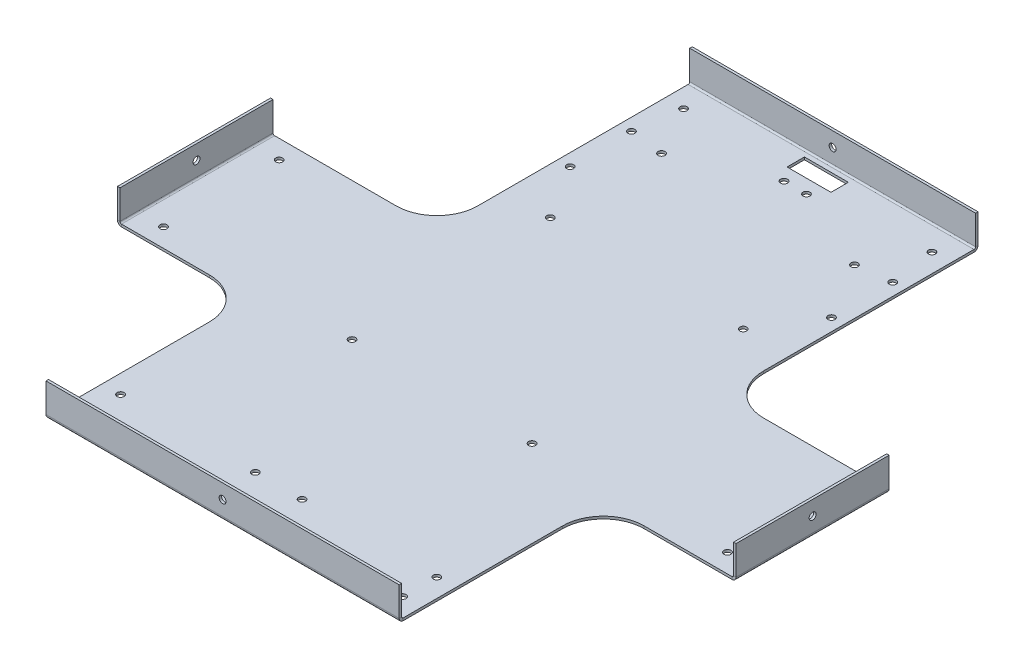
SolidWorks part; units mm, degrees
note: The reader was unsure of these and kept them because the rebuilt part matched: flange length of "Edge-Flange1", "Edge-Flange2", "Edge-Flange3".
material "Plain Carbon Steel"
ref_plane "Front Plane" through (0, 0, 0) normal (0, 0, 1) x (1, 0, 0)
ref_plane "Top Plane" through (0, 0, 0) normal (0, 1, 0) x (1, 0, 0)
ref_plane "Right Plane" through (0, 0, 0) normal (1, 0, 0) x (0, 0, -1)
sketch "Sketch1" plane through (0, 0, 0) normal (0, 1, 0) x (1, 0, 0)
  line L0 (86.5, 300) -> (86.5, 0) construction
  line L1 (0, 0) -> (173, 0)
  line L2 (0, 0) -> (0, 100)
  line L3 (16.5, 300) -> (156.5, 300)
  line L4 (173, 0) -> (173, 100)
  line L6 (0, 100) -> (-65, 100)
  line L7 (156.5, 175) -> (156.5, 300)
  line L8 (16.5, 175) -> (-65, 175)
  line L9 (-65, 100) -> (-65, 175)
  line L10 (16.5, 175) -> (16.5, 300)
  line L11 (156.5, 175) -> (238, 175)
  line L13 (173, 100) -> (238, 100)
  line L14 (238, 175) -> (238, 100)
  dimension "D1" = 300
  dimension "D2" = 173
  dimension "D3" = 100
  dimension "D4" = 65
  dimension "D5" = 125
  dimension "D6" = 100
  dimension "D7" = 125
  dimension "D8" = 65
  dimension "D9" = 140
base flange "Base-Flange1" sketch "Sketch1" thickness 1.21 reverse thickness direction no parameters "D1"=0.762
ref_plane "Mid Width Plane" through (86.5, 0, 0) normal (1, 0, 0) x (0, 0, -1)
hole_wizard "M3 Clearance Hole2" positions "Sketch29" profile "Sketch28" hole size "M3" standard "ANSI Metric"
sketch "Sketch29" plane through (0, -1.21, 0) normal (0, -1, 0) x (-1, 0, 0)
  point P0 (-9.052, 27.4796)
  point P3 (-75.052, 27.4796)
  point P6 (-42.4171, 107.4796)
sketch "Sketch28" plane through (9.052, -1.21, -27.4796) normal (1, 0, 0) x (0, 0, -1)
  line L0 (0, 0) -> (0, 2.2915)
  line L1 (0, 2.2915) -> (1.7, 1.27)
  line L2 (1.7, 1.27) -> (1.7, 0)
  line L5 (1.7, 0) -> (0, 0)
  line L10 (0, 2.2915) -> (-1.7, 1.27) construction
  line L11 (0, -6.35) -> (0, 107.95) construction
  dimension "Hole Dia." = 3.4
  dimension "Hole Depth" = 1.27
  dimension "Drill Angle" = 118
mirror "Mirror3" about plane through (86.5, 0, 0) normal (1, 0, 0) of "M3 Clearance Hole2"
fillet "Fillet1" radius 20 4 edges at (0, -0.605, -100) (173, -0.605, -100) (156.5, -0.605, -175) (16.5, -0.605, -175)
sketch "Sketch34" plane through (0, 0, 0) normal (0, 1, 0) x (1, 0, 0)
  line L0 (4.104, 114.5316) -> (80, 114.5316) construction
  line L1 (140.5, 119.5316) -> (32.5, 119.5316)
  line L2 (140.5, 119.5316) -> (140.5, 214.5316)
  line L3 (140.5, 214.5316) -> (32.5, 214.5316)
  line L4 (32.5, 119.5316) -> (32.5, 214.5316)
  line L5 (140.5, 119.5316) -> (32.5, 214.5316) construction
  line L6 (140.5, 214.5316) -> (32.5, 119.5316) construction
  line L9 (238, 100) -> (238, 175) construction
  point P0 (86.5, 167.0316)
  dimension "D1" = 95
  dimension "D2" = 108
  dimension "D3" = 52.5
  dimension "D4" = 151.5
sketch "Sketch35" plane through (0, 0, 0) normal (0, 1, 0) x (1, 0, 0)
  line L0 (140.5, 119.5316) -> (32.5, 119.5316) construction
  line L1 (147.5, 119.5316) -> (25.5, 119.5316)
  line L2 (147.5, 119.5316) -> (147.5, 132.5316)
  line L3 (147.5, 132.5316) -> (25.5, 132.5316)
  line L4 (25.5, 119.5316) -> (25.5, 132.5316)
  line L5 (147.5, 119.5316) -> (25.5, 132.5316) construction
  line L6 (147.5, 132.5316) -> (25.5, 119.5316) construction
  line L7 (32.5, 119.5316) -> (32.5, 214.5316) construction
  point P0 (86.5, 126.0316)
  dimension "D1" = 122
  dimension "D2" = 13
  dimension "D3" = 0
  dimension "D4" = 7
sketch "Sketch62" plane through (0, 0, 0) normal (0, 1, 0) x (1, 0, 0)
  line L0 (86.5, -55.3673) -> (86.5, 55.3673) construction
  line L1 (138.897, 204.6283) -> (38.2926, 204.6283)
  line L2 (138.897, 204.6283) -> (138.897, 264.6283)
  line L3 (138.897, 264.6283) -> (38.2926, 264.6283)
  line L4 (38.2926, 204.6283) -> (38.2926, 264.6283)
  line L5 (138.897, 204.6283) -> (38.2926, 264.6283) construction
  line L6 (138.897, 264.6283) -> (38.2926, 204.6283) construction
  line L7 (97.25, 295.738) -> (75.75, 295.738)
  line L8 (97.25, 295.738) -> (97.25, 287.238)
  line L9 (97.25, 287.238) -> (75.75, 287.238)
  line L10 (75.75, 295.738) -> (75.75, 287.238)
  line L11 (97.25, 295.738) -> (75.75, 287.238) construction
  line L12 (97.25, 287.238) -> (75.75, 295.738) construction
  line L14 (156.5, 300) -> (16.5, 300) construction
  point P0 (88.5948, 234.6283)
  point P5 (86.5, 291.488)
  dimension "D1" = 60
  dimension "D2" = 8.5
  dimension "D3" = 21.5
  dimension "D4" = 0
  dimension "D5" = 4.262
extrude "QRD Clearance" cut sketch "Sketch62" against normal blind 10 contours L10 L9 L8 L7 normal cut yes
sketch "Steering Box Allocation" plane through (0, 0, 0) normal (0, 1, 0) x (1, 0, 0)
  line L1 (161.5, 221.5316) -> (11.5, 221.5316)
  line L2 (161.5, 221.5316) -> (161.5, 291.5316)
  line L3 (161.5, 291.5316) -> (11.5, 291.5316)
  line L4 (11.5, 221.5316) -> (11.5, 291.5316)
  line L5 (161.5, 221.5316) -> (11.5, 291.5316) construction
  line L6 (161.5, 291.5316) -> (11.5, 221.5316) construction
  line L8 (140.5, 214.5316) -> (32.5, 214.5316) construction
  line L10 (86.5, -55.3673) -> (86.5, 55.3673) construction
  point P0 (86.5, 256.5316)
  dimension "D1" = 150
  dimension "D2" = 0
  dimension "D3" = 70
  dimension "D4" = 7
hole_wizard "QRD Holes" positions "Sketch75" profile "Sketch74" hole size "M3" standard "ANSI Metric"
sketch "Sketch75" plane through (0, 0, 0) normal (0, 1, 0) x (1, 0, 0)
  point P0 (92, 280.488)
  point P3 (81, 280.488)
sketch "Sketch74" plane through (92, 0, -280.488) normal (1, 0, 0) x (0, 0, 1)
  line L0 (0, 0) -> (0, 2.2915)
  line L1 (0, 2.2915) -> (1.7, 1.27)
  line L2 (1.7, 1.27) -> (1.7, 0)
  line L5 (1.7, 0) -> (0, 0)
  line L10 (0, 2.2915) -> (-1.7, 1.27) construction
  line L11 (0, -6.35) -> (0, 107.95) construction
  dimension "Hole Dia." = 3.4
  dimension "Hole Depth" = 1.27
  dimension "Drill Angle" = 118
sketch "Sketch73" plane through (0, 0, 0) normal (0, 1, 0) x (1, 0, 0)
  line L0 (16.5, 249.238) -> (200, 249.238)
  line L1 (16.5, 299.238) -> (16.5, 195) construction
  line L3 (16.5, 299.238) -> (156.5, 299.238) construction
  dimension "D1" = 50
hole_wizard "M3 (Steering Box)" positions "Sketch133" profile "Sketch132" hole size "M3" standard "ANSI Metric"
sketch "Sketch133" plane through (0, 0, 0) normal (0, 1, 0) x (1, 0, 0)
  point P0 (39.262, 262.238)
  point P3 (39.262, 207.762)
  point P6 (133.738, 207.762)
  point P9 (133.738, 262.238)
sketch "Sketch132" plane through (39.262, 0, -262.238) normal (1, 0, 0) x (0, 0, 1)
  line L0 (0, 0) -> (0, 4.0215)
  line L1 (0, 4.0215) -> (1.7, 3)
  line L2 (1.7, 3) -> (1.7, 0)
  line L5 (1.7, 0) -> (0, 0)
  line L10 (0, 4.0215) -> (-1.7, 3) construction
  line L11 (0, -6.35) -> (0, 107.95) construction
  dimension "Hole Dia." = 3.4
  dimension "Hole Depth" = 3
  dimension "Drill Angle" = 118
edge flange "Edge-Flange1" sketch "Sketch136" flange angle 90 flange length 15 flange position material inside bend radius 0.762 thickness 1.21 relief rectangular parameters "D6"=10
sketch "Sketch136" plane through (0, 0, 0) normal (0, 0, 1) x (1, 0, 0)
  line L2 (0, 0) -> (0, 15)
  line L3 (0, 15) -> (173, 15)
  line L4 (173, 15) -> (173, 0)
  line L5 (0, 0) -> (173, 0) construction
  line L6 (0, 0) -> (173, 0)
bend "EdgeBend1" bend radius 0.762 bend angle 90 parameters "D5"=1
edge flange "Edge-Flange2" sketch "Sketch139" flange angle 90 flange length 15 flange position material inside bend radius 0.762 thickness 1.21 relief rectangular parameters "D6"=10
sketch "Sketch139" plane through (0, 0, -300) normal (0, 0, -1) x (-1, 0, 0)
  line L0 (-156.5, 0) -> (-16.5, 0) construction
  line L1 (-156.5, 0) -> (-16.5, 0)
  line L2 (-156.5, 0) -> (-156.5, 15)
  line L3 (-156.5, 15) -> (-16.5, 15)
  line L4 (-16.5, 15) -> (-16.5, 0)
bend "EdgeBend2" bend radius 0.762 bend angle 90 parameters "D5"=2
edge flange "Edge-Flange3" sketch "Sketch142" flange angle 90 flange length 15 flange position material inside bend radius 0.762 thickness 1.21 relief rectangular parameters "D6"=10
sketch "Sketch142" plane through (238, 0, 0) normal (1, 0, 0) x (0, 0, -1)
  line L2 (100, 0) -> (100, 15)
  line L3 (100, 15) -> (175, 15)
  line L4 (175, 15) -> (175, 0)
  line L5 (100, 0) -> (175, 0) construction
  line L6 (100, 0) -> (175, 0)
bend "EdgeBend3" bend radius 0.762 bend angle 90 parameters "D5"=3
mirror "Mirror4" about plane through (86.5, 0, 0) normal (1, 0, 0) of "Edge-Flange3"
bend "MirrorBend1" bend radius 0.762 bend angle 90 parameters "D5"=4
hole_wizard "M3 Clearance Hole3" positions "Sketch143" profile "Sketch144" hole size "M3" standard "ANSI Metric" end condition through all
sketch "Sketch143" plane through (50.7661, 0, -139.8998) normal (0, 1, 0) x (1, 0, 0)
  point P0 (-28.2661, 124.3382)
  point P1 (-28.2661, 94.3382)
sketch "Sketch144" plane through (22.5, 0, -264.238) normal (1, 0, 0) x (0, 0, 1)
  line L0 (0, 0) -> (0, 1.21)
  line L1 (0, 1.21) -> (1.7, 1.21)
  line L2 (1.7, 1.21) -> (1.7, 0)
  line L3 (1.7, 0) -> (0, 0)
  line L4 (0, -6.35) -> (0, 107.95) construction
  dimension "Thru Hole Dia." = 3.4
  dimension "Thru Hole Depth" = 1.21
hole_wizard "M3 Clearance Hole4" positions "Sketch145" profile "Sketch146" hole size "M3" standard "ANSI Metric" end condition through all
sketch "Sketch145" plane through (50.7661, 0, -139.8998) normal (0, 1, 0) x (1, 0, 0)
  point P0 (99.7339, 124.3382)
  point P1 (99.7339, 94.3382)
sketch "Sketch146" plane through (150.5, 0, -264.238) normal (1, 0, 0) x (0, 0, 1)
  line L0 (0, 0) -> (0, 1.21)
  line L1 (0, 1.21) -> (1.7, 1.21)
  line L2 (1.7, 1.21) -> (1.7, 0)
  line L3 (1.7, 0) -> (0, 0)
  line L4 (0, -6.35) -> (0, 107.95) construction
  dimension "Thru Hole Dia." = 3.4
  dimension "Thru Hole Depth" = 1.21
hole_wizard "M3 Clearance Hole5" positions "Sketch148" profile "Sketch147" hole size "M3" standard "ANSI Metric" end condition up to next
sketch "Sketch148" plane through (0, 0, 0) normal (0, 0, 1) x (1, 0, 0)
  line L2 (86.5, 15) -> (86.5, 0.762) construction
  line L3 (173, 15) -> (0, 15) construction
  line L4 (173, 0.762) -> (0, 0.762) construction
  line L7 (173, 7.881) -> (0, 7.881) construction
  line L8 (173, 0.762) -> (173, 15) construction
  line L9 (0, 15) -> (0, 0.762) construction
  point P0 (86.5, 7.881)
sketch "Sketch147" plane through (86.5, 7.881, 0) normal (1, 0, 0) x (0, -1, 0)
  line L0 (0, 0) -> (0, 1.21)
  line L1 (0, 1.21) -> (1.7, 1.21)
  line L2 (1.7, 1.21) -> (1.7, 0)
  line L5 (1.7, 0) -> (0, 0)
  line L11 (0, -6.35) -> (0, 107.95) construction
  dimension "Thru Hole Dia." = 3.4
  dimension "Thru Hole Depth" = 1.21
hole_wizard "M3 Clearance Hole6" positions "Sketch150" profile "Sketch149" hole size "M3" standard "ANSI Metric" end condition through all
sketch "Sketch150" plane through (238, 0, 0) normal (1, 0, 0) x (0, 0, -1)
  line L0 (100, 7.881) -> (175, 7.881) construction
  line L1 (100, 15) -> (100, 0.762) construction
  line L2 (175, 0.762) -> (175, 15) construction
  line L4 (137.5, 15) -> (137.5, 0.762) construction
  line L5 (175, 15) -> (100, 15) construction
  line L6 (175, 0.762) -> (100, 0.762) construction
  point P0 (137.5, 7.881)
sketch "Sketch149" plane through (238, 7.881, -137.5) normal (0, 1, 0) x (0, 0, -1)
  line L0 (0, 0) -> (0, 303)
  line L1 (0, 303) -> (1.7, 303)
  line L2 (1.7, 303) -> (1.7, 0)
  line L5 (1.7, 0) -> (0, 0)
  line L11 (0, -6.35) -> (0, 107.95) construction
  dimension "Thru Hole Dia." = 3.4
  dimension "Thru Hole Depth" = 303
hole_wizard "M3 Clearance Hole7" positions "Sketch154" profile "Sketch153" hole size "M3" standard "ANSI Metric"
sketch "Sketch154" plane through (0, 0, -300) normal (0, 0, -1) x (-1, 0, 0)
  line L0 (-156.5, 7.881) -> (-16.5, 7.881) construction
  line L1 (-156.5, 15) -> (-156.5, 0.762) construction
  line L2 (-16.5, 0.762) -> (-16.5, 15) construction
  line L4 (-86.5, 15) -> (-86.5, 0.762) construction
  line L5 (-16.5, 15) -> (-156.5, 15) construction
  line L6 (-16.5, 0.762) -> (-156.5, 0.762) construction
  point P0 (-86.5, 7.881)
sketch "Sketch153" plane through (86.5, 7.881, -300) normal (1, 0, 0) x (0, 1, 0)
  line L0 (0, 0) -> (0, 2.2315)
  line L1 (0, 2.2315) -> (1.7, 1.21)
  line L2 (1.7, 1.21) -> (1.7, 0)
  line L5 (1.7, 0) -> (0, 0)
  line L10 (0, 2.2315) -> (-1.7, 1.21) construction
  line L11 (0, -6.35) -> (0, 107.95) construction
  dimension "Hole Dia." = 3.4
  dimension "Hole Depth" = 1.21
  dimension "Drill Angle" = 118
hole_wizard "M3 Clearance Hole8" positions "Sketch155" profile "Sketch156" hole size "M3" standard "ANSI Metric" end condition through all
sketch "Sketch155" plane through (50.7661, 0, -139.8998) normal (0, 1, 0) x (1, 0, 0)
  point P0 (-25.0951, 146.7192)
  point P1 (96.5629, 146.7192)
sketch "Sketch156" plane through (25.671, 0, -286.619) normal (1, 0, 0) x (0, 0, 1)
  line L0 (0, 0) -> (0, 1.21)
  line L1 (0, 1.21) -> (1.7, 1.21)
  line L2 (1.7, 1.21) -> (1.7, 0)
  line L3 (1.7, 0) -> (0, 0)
  line L4 (0, -6.35) -> (0, 107.95) construction
  dimension "Thru Hole Dia." = 3.4
  dimension "Thru Hole Depth" = 1.21
hole_wizard "M3 Clearance Hole9" positions "Sketch157" profile "Sketch158" hole size "M3" standard "ANSI Metric" end condition through all
sketch "Sketch157" plane through (50.7661, 0, -139.8998) normal (0, 1, 0) x (1, 0, 0)
  point P0 (-102.3851, -30.7288)
  point P1 (-102.3851, 25.9292)
sketch "Sketch158" plane through (-51.619, 0, -109.171) normal (1, 0, 0) x (0, 0, 1)
  line L0 (0, 0) -> (0, 1.21)
  line L1 (0, 1.21) -> (1.7, 1.21)
  line L2 (1.7, 1.21) -> (1.7, 0)
  line L3 (1.7, 0) -> (0, 0)
  line L4 (0, -6.35) -> (0, 107.95) construction
  dimension "Thru Hole Dia." = 3.4
  dimension "Thru Hole Depth" = 1.21
hole_wizard "M3 Clearance Hole10" positions "Sketch159" profile "Sketch160" hole size "M3" standard "ANSI Metric" end condition through all
sketch "Sketch159" plane through (50.7661, 0, -139.8998) normal (0, 1, 0) x (1, 0, 0)
  point P0 (173.8529, 25.9292)
  point P1 (173.8529, -30.7288)
sketch "Sketch160" plane through (224.619, 0, -165.829) normal (1, 0, 0) x (0, 0, 1)
  line L0 (0, 0) -> (0, 1.21)
  line L1 (0, 1.21) -> (1.7, 1.21)
  line L2 (1.7, 1.21) -> (1.7, 0)
  line L3 (1.7, 0) -> (0, 0)
  line L4 (0, -6.35) -> (0, 107.95) construction
  dimension "Thru Hole Dia." = 3.4
  dimension "Thru Hole Depth" = 1.21
hole_wizard "M3 Clearance Hole11" positions "Sketch161" profile "Sketch162" hole size "M3" standard "ANSI Metric" end condition through all
sketch "Sketch161" plane through (50.7661, 0, -139.8998) normal (0, 1, 0) x (1, 0, 0)
  point P0 (113.0629, -129.0188)
  point P1 (-41.5951, -129.0188)
sketch "Sketch162" plane through (163.829, 0, -10.881) normal (1, 0, 0) x (0, 0, 1)
  line L0 (0, 0) -> (0, 1.21)
  line L1 (0, 1.21) -> (1.7, 1.21)
  line L2 (1.7, 1.21) -> (1.7, 0)
  line L3 (1.7, 0) -> (0, 0)
  line L4 (0, -6.35) -> (0, 107.95) construction
  dimension "Thru Hole Dia." = 3.4
  dimension "Thru Hole Depth" = 1.21
sketch "Bend-Lines1" [suppressed] plane through (0, 0, 0) normal (0, 1, 0) x (1, 0, 0)
sketch "Bounding-Box1" [suppressed] plane through (0, 0, 0) normal (0, 1, 0) x (1, 0, 0)
sheet metal parameters "Sheet-Metal(1)" thickness 1.21 parameters "D1"=0.762
flat pattern "Flat-Pattern(1)" [suppressed]
sketch "Bend-Lines2" plane through (0, 0, 0) normal (0, 1, 0) x (1, 0, 0)
sketch "Bounding-Box2" [suppressed] plane through (0, 0, 0) normal (0, 1, 0) x (1, 0, 0)
sheet metal parameters "Sheet-Metal(23)" thickness 1.21 parameters "D1"=0.762
flat pattern "Flat-Pattern(1)"
sketch "Bend-Lines2" plane through (0, 0, 0) normal (0, 1, 0) x (1, 0, 0)
sketch "Bounding-Box2" [suppressed] plane through (0, 0, 0) normal (0, 1, 0) x (1, 0, 0)
sheet metal parameters "Sheet-Metal(24)" thickness 1.21 parameters "D1"=0.762
flat pattern "Flat-Pattern(1)"
sketch "Bend-Lines2" plane through (0, 0, 0) normal (0, 1, 0) x (1, 0, 0)
sketch "Bounding-Box2" [suppressed] plane through (0, 0, 0) normal (0, 1, 0) x (1, 0, 0)
sheet metal parameters "Sheet-Metal(36)" thickness 1.21 parameters "D1"=0.762
flat pattern "Flat-Pattern(1)"
sketch "Bend-Lines2" plane through (0, 0, 0) normal (0, 1, 0) x (1, 0, 0)
sketch "Bounding-Box2" [suppressed] plane through (0, 0, 0) normal (0, 1, 0) x (1, 0, 0)
sheet metal parameters "Sheet-Metal(39)" thickness 1.21 parameters "D1"=0.762
flat pattern "Flat-Pattern(1)"
sketch "Bend-Lines2" plane through (0, 0, 0) normal (0, 1, 0) x (1, 0, 0)
sketch "Bounding-Box2" [suppressed] plane through (0, 0, 0) normal (0, 1, 0) x (1, 0, 0)
sheet metal parameters "Sheet-Metal(71)" thickness 1.21 parameters "D1"=0.762
flat pattern "Flat-Pattern(1)"
sketch "Bend-Lines2" plane through (0, 0, 0) normal (0, 1, 0) x (1, 0, 0)
  line L0 (0, -74.1425) -> (173, -74.1425) construction
  line L1 (372.6314, 94.104) -> (372.6314, 200) construction
  line L2 (352.7291, 94.104) -> (352.7291, 200) construction
  line L3 (331.5548, 94.104) -> (331.5548, 200) construction
  line L4 (-199.6314, 200) -> (-199.6314, 94.104) construction
  line L5 (-179.7291, 200) -> (-179.7291, 94.104) construction
  line L6 (-158.5548, 200) -> (-158.5548, 94.104) construction
  line L7 (173, 372.3805) -> (0, 372.3805) construction
  line L8 (310.3805, 94.104) -> (310.3805, 200) construction
  line L9 (-137.3805, 200) -> (-137.3805, 94.104) construction
  line L10 (147.5, 100.0722) -> (25.5, 100.0722) construction
  line L11 (0, -1.9682) -> (173, -1.9682) construction
  line L12 (-65.2062, 200) -> (-65.2062, 94.104) construction
  line L13 (173, 300.2062) -> (0, 300.2062) construction
  line L14 (238.2062, 94.104) -> (238.2062, 200) construction
  line L15 (0, -74.1425) -> (173, -74.1425) construction
  line L16 (372.6314, 94.104) -> (372.6314, 200) construction
  line L17 (352.7291, 94.104) -> (352.7291, 200) construction
  line L18 (331.5548, 94.104) -> (331.5548, 200) construction
  line L19 (-199.6314, 200) -> (-199.6314, 94.104) construction
  line L20 (-179.7291, 200) -> (-179.7291, 94.104) construction
  line L21 (-158.5548, 200) -> (-158.5548, 94.104) construction
  line L22 (173, 372.3805) -> (0, 372.3805) construction
  line L23 (310.3805, 94.104) -> (310.3805, 200) construction
  line L24 (-137.3805, 200) -> (-137.3805, 94.104) construction
  line L25 (147.5, 100.0722) -> (25.5, 100.0722) construction
  line L26 (0, -1.9682) -> (173, -1.9682) construction
  line L27 (-65.2062, 200) -> (-65.2062, 94.104) construction
  line L28 (173, 300.2062) -> (0, 300.2062) construction
  line L29 (238.2062, 94.104) -> (238.2062, 200) construction
sketch3d "Bounding-Box2" [suppressed]
  line L0 (-268.2639, 140.3537, 0) -> (126.5382, -205.5089, 0) construction
  line L1 (46.4618, 499.6129, 0) -> (441.2639, 153.7503, 0) construction
  line L2 (-268.2639, 140.3537, 0) -> (46.4618, 499.6129, 0) construction
  line L3 (126.5382, -205.5089, 0) -> (441.2639, 153.7503, 0) construction
sheet metal parameters "Sheet-Metal(103)" thickness 1.21 parameters "D1"=0.762
flat pattern "Flat-Pattern(1)" [suppressed]
sketch "Bend-Lines2" plane through (0, 0, 0) normal (0, 1, 0) x (1, 0, 0)
  line L0 (0, -74.1425) -> (173, -74.1425) construction
  line L1 (372.6314, 94.104) -> (372.6314, 200) construction
  line L2 (352.7291, 94.104) -> (352.7291, 200) construction
  line L3 (331.5548, 94.104) -> (331.5548, 200) construction
  line L4 (-199.6314, 200) -> (-199.6314, 94.104) construction
  line L5 (-179.7291, 200) -> (-179.7291, 94.104) construction
  line L6 (-158.5548, 200) -> (-158.5548, 94.104) construction
  line L7 (173, 372.3805) -> (0, 372.3805) construction
  line L8 (310.3805, 94.104) -> (310.3805, 200) construction
  line L9 (-137.3805, 200) -> (-137.3805, 94.104) construction
  line L10 (147.5, 100.0722) -> (25.5, 100.0722) construction
  line L11 (0, -1.9682) -> (173, -1.9682) construction
  line L12 (-65.2062, 200) -> (-65.2062, 94.104) construction
  line L13 (173, 300.2062) -> (0, 300.2062) construction
  line L14 (238.2062, 94.104) -> (238.2062, 200) construction
  line L15 (0, -74.1425) -> (173, -74.1425) construction
  line L16 (372.6314, 94.104) -> (372.6314, 200) construction
  line L17 (352.7291, 94.104) -> (352.7291, 200) construction
  line L18 (331.5548, 94.104) -> (331.5548, 200) construction
  line L19 (-199.6314, 200) -> (-199.6314, 94.104) construction
  line L20 (-179.7291, 200) -> (-179.7291, 94.104) construction
  line L21 (-158.5548, 200) -> (-158.5548, 94.104) construction
  line L22 (173, 372.3805) -> (0, 372.3805) construction
  line L23 (310.3805, 94.104) -> (310.3805, 200) construction
  line L24 (-137.3805, 200) -> (-137.3805, 94.104) construction
  line L25 (147.5, 100.0722) -> (25.5, 100.0722) construction
  line L26 (0, -1.9682) -> (173, -1.9682) construction
  line L27 (-65.2062, 200) -> (-65.2062, 94.104) construction
  line L28 (173, 300.2062) -> (0, 300.2062) construction
  line L29 (238.2062, 94.104) -> (238.2062, 200) construction
sketch3d "Bounding-Box2" [suppressed]
  line L0 (-268.2639, 140.3537, 0) -> (126.5382, -205.5089, 0) construction
  line L1 (46.4618, 499.6129, 0) -> (441.2639, 153.7503, 0) construction
  line L2 (-268.2639, 140.3537, 0) -> (46.4618, 499.6129, 0) construction
  line L3 (126.5382, -205.5089, 0) -> (441.2639, 153.7503, 0) construction
bend of the flat pattern "Flatten-<EdgeBend1>1"
sheet metal parameters "Sheet-Metal(104)" thickness 1.21 parameters "D1"=0.762
flat pattern "Flat-Pattern(1)"
sketch "Bend-Lines2" plane through (0, 0, 0) normal (0, 1, 0) x (1, 0, 0)
  line L30 (18.5, 298.9962) -> (154.5, 298.9962) construction
  line L31 (171, 1.0038) -> (2, 1.0038) construction
  line L32 (18.5, 298.9962) -> (154.5, 298.9962) construction
  line L33 (171, 1.0038) -> (2, 1.0038) construction
sketch3d "Bounding-Box2" [suppressed]
  line L0 (238.0001, 314.2023, 0) -> (237.9999, -14.2023, 0) construction
  line L1 (-64.9999, 314.2024, 0) -> (-65.0001, -14.2022, 0) construction
  line L2 (238.0001, 314.2023, 0) -> (-64.9999, 314.2024, 0) construction
  line L3 (237.9999, -14.2023, 0) -> (-65.0001, -14.2022, 0) construction
bend of the flat pattern "Flatten-<EdgeBend1>1"
bend of the flat pattern "Flatten-<EdgeBend2>1"
sheet metal parameters "Sheet-Metal(105)" thickness 1.21 parameters "D1"=0.762
flat pattern "Flat-Pattern(1)" [suppressed]
sketch "Bend-Lines2" plane through (0, 0, 0) normal (0, 1, 0) x (1, 0, 0)
  line L30 (18.5, 298.9962) -> (154.5, 298.9962) construction
  line L31 (171, 1.0038) -> (2, 1.0038) construction
  line L32 (18.5, 298.9962) -> (154.5, 298.9962) construction
  line L33 (171, 1.0038) -> (2, 1.0038) construction
sketch3d "Bounding-Box2" [suppressed]
  line L0 (238.0001, 314.2023, 0) -> (237.9999, -14.2023, 0) construction
  line L1 (-64.9999, 314.2024, 0) -> (-65.0001, -14.2022, 0) construction
  line L2 (238.0001, 314.2023, 0) -> (-64.9999, 314.2024, 0) construction
  line L3 (237.9999, -14.2023, 0) -> (-65.0001, -14.2022, 0) construction
bend of the flat pattern "Flatten-<EdgeBend1>1"
bend of the flat pattern "Flatten-<EdgeBend3>1"
bend of the flat pattern "Flatten-<EdgeBend2>1"
sheet metal parameters "Sheet-Metal(106)" thickness 1.21 parameters "D1"=0.762
flat pattern "Flat-Pattern(1)" [suppressed]
sketch "Bend-Lines2" plane through (0, 0, 0) normal (0, 1, 0) x (1, 0, 0)
  line L30 (18.5, 298.9962) -> (154.5, 298.9962) construction
  line L31 (171, 1.0038) -> (2, 1.0038) construction
  line L32 (18.5, 298.9962) -> (154.5, 298.9962) construction
  line L33 (171, 1.0038) -> (2, 1.0038) construction
sketch3d "Bounding-Box2" [suppressed]
  line L0 (238.0001, 314.2023, 0) -> (237.9999, -14.2023, 0) construction
  line L1 (-64.9999, 314.2024, 0) -> (-65.0001, -14.2022, 0) construction
  line L2 (238.0001, 314.2023, 0) -> (-64.9999, 314.2024, 0) construction
  line L3 (237.9999, -14.2023, 0) -> (-65.0001, -14.2022, 0) construction
bend of the flat pattern "Flatten-<EdgeBend1>1"
bend of the flat pattern "Flatten-<EdgeBend3>1"
bend of the flat pattern "Flatten-<MirrorBend1>1"
bend of the flat pattern "Flatten-<EdgeBend2>1"
sheet metal parameters "Sheet-Metal(107)" thickness 1.21 parameters "D1"=0.762
flat pattern "Flat-Pattern(1)" [suppressed]
sketch "Bend-Lines2" plane through (0, 0, 0) normal (0, 1, 0) x (1, 0, 0)
  line L30 (18.5, 298.9962) -> (154.5, 298.9962) construction
  line L31 (171, 1.0038) -> (2, 1.0038) construction
  line L32 (18.5, 298.9962) -> (154.5, 298.9962) construction
  line L33 (171, 1.0038) -> (2, 1.0038) construction
sketch3d "Bounding-Box2" [suppressed]
  line L0 (238.0001, 314.2023, 0) -> (237.9999, -14.2023, 0) construction
  line L1 (-64.9999, 314.2024, 0) -> (-65.0001, -14.2022, 0) construction
  line L2 (238.0001, 314.2023, 0) -> (-64.9999, 314.2024, 0) construction
  line L3 (237.9999, -14.2023, 0) -> (-65.0001, -14.2022, 0) construction
bend of the flat pattern "Flatten-<EdgeBend1>1"
bend of the flat pattern "Flatten-<EdgeBend3>1"
bend of the flat pattern "Flatten-<MirrorBend1>1"
bend of the flat pattern "Flatten-<EdgeBend2>1"
sheet metal parameters "Sheet-Metal(108)" thickness 1.21 parameters "D1"=0.762
flat pattern "Flat-Pattern(1)" [suppressed]
sketch "Bend-Lines2" plane through (0, 0, 0) normal (0, 1, 0) x (1, 0, 0)
  line L30 (18.5, 298.9962) -> (154.5, 298.9962) construction
  line L31 (171, 1.0038) -> (2, 1.0038) construction
  line L32 (18.5, 298.9962) -> (154.5, 298.9962) construction
  line L33 (171, 1.0038) -> (2, 1.0038) construction
sketch3d "Bounding-Box2" [suppressed]
  line L0 (238.0001, 314.2023, 0) -> (237.9999, -14.2023, 0) construction
  line L1 (-64.9999, 314.2024, 0) -> (-65.0001, -14.2022, 0) construction
  line L2 (238.0001, 314.2023, 0) -> (-64.9999, 314.2024, 0) construction
  line L3 (237.9999, -14.2023, 0) -> (-65.0001, -14.2022, 0) construction
bend of the flat pattern "Flatten-<EdgeBend1>1"
bend of the flat pattern "Flatten-<EdgeBend3>1"
bend of the flat pattern "Flatten-<MirrorBend1>1"
bend of the flat pattern "Flatten-<EdgeBend2>1"
sheet metal parameters "Sheet-Metal(109)" thickness 1.21 parameters "D1"=0.762
flat pattern "Flat-Pattern(1)" [suppressed]
sketch "Bend-Lines2" plane through (0, 0, 0) normal (0, 1, 0) x (1, 0, 0)
  line L30 (18.5, 298.9962) -> (154.5, 298.9962) construction
  line L31 (171, 1.0038) -> (2, 1.0038) construction
  line L32 (18.5, 298.9962) -> (154.5, 298.9962) construction
  line L33 (171, 1.0038) -> (2, 1.0038) construction
sketch3d "Bounding-Box2" [suppressed]
  line L0 (238.0001, 314.2023, 0) -> (237.9999, -14.2023, 0) construction
  line L1 (-64.9999, 314.2024, 0) -> (-65.0001, -14.2022, 0) construction
  line L2 (238.0001, 314.2023, 0) -> (-64.9999, 314.2024, 0) construction
  line L3 (237.9999, -14.2023, 0) -> (-65.0001, -14.2022, 0) construction
bend of the flat pattern "Flatten-<EdgeBend1>1"
bend of the flat pattern "Flatten-<EdgeBend3>1"
bend of the flat pattern "Flatten-<MirrorBend1>1"
bend of the flat pattern "Flatten-<EdgeBend2>1"
sheet metal parameters "Sheet-Metal(110)" thickness 1.21 parameters "D1"=0.762
flat pattern "Flat-Pattern(1)" [suppressed]
sketch "Bend-Lines2" plane through (0, 0, 0) normal (0, 1, 0) x (1, 0, 0)
  line L30 (18.5, 298.9962) -> (154.5, 298.9962) construction
  line L31 (171, 1.0038) -> (2, 1.0038) construction
  line L32 (18.5, 298.9962) -> (154.5, 298.9962) construction
  line L33 (171, 1.0038) -> (2, 1.0038) construction
sketch3d "Bounding-Box2" [suppressed]
  line L0 (238.0001, 314.2023, 0) -> (237.9999, -14.2023, 0) construction
  line L1 (-64.9999, 314.2024, 0) -> (-65.0001, -14.2022, 0) construction
  line L2 (238.0001, 314.2023, 0) -> (-64.9999, 314.2024, 0) construction
  line L3 (237.9999, -14.2023, 0) -> (-65.0001, -14.2022, 0) construction
bend of the flat pattern "Flatten-<EdgeBend1>1"
bend of the flat pattern "Flatten-<EdgeBend3>1"
bend of the flat pattern "Flatten-<MirrorBend1>1"
bend of the flat pattern "Flatten-<EdgeBend2>1"
sheet metal parameters "Sheet-Metal(111)" thickness 1.21 parameters "D1"=0.762
flat pattern "Flat-Pattern(1)" [suppressed]
sketch "Bend-Lines2" plane through (0, 0, 0) normal (0, 1, 0) x (1, 0, 0)
  line L30 (18.5, 298.9962) -> (154.5, 298.9962) construction
  line L31 (171, 1.0038) -> (2, 1.0038) construction
  line L32 (18.5, 298.9962) -> (154.5, 298.9962) construction
  line L33 (171, 1.0038) -> (2, 1.0038) construction
sketch3d "Bounding-Box2" [suppressed]
  line L0 (238.0001, 314.2023, 0) -> (237.9999, -14.2023, 0) construction
  line L1 (-64.9999, 314.2024, 0) -> (-65.0001, -14.2022, 0) construction
  line L2 (238.0001, 314.2023, 0) -> (-64.9999, 314.2024, 0) construction
  line L3 (237.9999, -14.2023, 0) -> (-65.0001, -14.2022, 0) construction
bend of the flat pattern "Flatten-<EdgeBend1>1"
bend of the flat pattern "Flatten-<EdgeBend3>1"
bend of the flat pattern "Flatten-<MirrorBend1>1"
bend of the flat pattern "Flatten-<EdgeBend2>1"
sheet metal parameters "Sheet-Metal(112)" thickness 1.21 parameters "D1"=0.762
flat pattern "Flat-Pattern(1)" [suppressed]
sketch "Bend-Lines2" plane through (0, 0, 0) normal (0, 1, 0) x (1, 0, 0)
  line L30 (18.5, 298.9962) -> (154.5, 298.9962) construction
  line L31 (171, 1.0038) -> (2, 1.0038) construction
  line L32 (18.5, 298.9962) -> (154.5, 298.9962) construction
  line L33 (171, 1.0038) -> (2, 1.0038) construction
sketch3d "Bounding-Box2" [suppressed]
  line L0 (238.0001, 314.2023, 0) -> (237.9999, -14.2023, 0) construction
  line L1 (-64.9999, 314.2024, 0) -> (-65.0001, -14.2022, 0) construction
  line L2 (238.0001, 314.2023, 0) -> (-64.9999, 314.2024, 0) construction
  line L3 (237.9999, -14.2023, 0) -> (-65.0001, -14.2022, 0) construction
bend of the flat pattern "Flatten-<EdgeBend1>1"
bend of the flat pattern "Flatten-<EdgeBend3>1"
bend of the flat pattern "Flatten-<MirrorBend1>1"
bend of the flat pattern "Flatten-<EdgeBend2>1"
sheet metal parameters "Sheet-Metal(113)" thickness 1.21 parameters "D1"=0.762
flat pattern "Flat-Pattern(1)" [suppressed]
sketch "Bend-Lines2" plane through (0, 0, 0) normal (0, 1, 0) x (1, 0, 0)
  line L30 (18.5, 298.9962) -> (154.5, 298.9962) construction
  line L31 (171, 1.0038) -> (2, 1.0038) construction
  line L32 (18.5, 298.9962) -> (154.5, 298.9962) construction
  line L33 (171, 1.0038) -> (2, 1.0038) construction
sketch3d "Bounding-Box2" [suppressed]
  line L0 (238.0001, 314.2023, 0) -> (237.9999, -14.2023, 0) construction
  line L1 (-64.9999, 314.2024, 0) -> (-65.0001, -14.2022, 0) construction
  line L2 (238.0001, 314.2023, 0) -> (-64.9999, 314.2024, 0) construction
  line L3 (237.9999, -14.2023, 0) -> (-65.0001, -14.2022, 0) construction
bend of the flat pattern "Flatten-<EdgeBend1>1"
bend of the flat pattern "Flatten-<EdgeBend3>1"
bend of the flat pattern "Flatten-<MirrorBend1>1"
bend of the flat pattern "Flatten-<EdgeBend2>1"
sheet metal parameters "Sheet-Metal(114)" thickness 1.21 parameters "D1"=0.762
flat pattern "Flat-Pattern(1)" [suppressed]
sketch "Bend-Lines2" plane through (0, 0, 0) normal (0, 1, 0) x (1, 0, 0)
  line L30 (18.5, 298.9962) -> (154.5, 298.9962) construction
  line L31 (171, 1.0038) -> (2, 1.0038) construction
  line L32 (18.5, 298.9962) -> (154.5, 298.9962) construction
  line L33 (171, 1.0038) -> (2, 1.0038) construction
sketch3d "Bounding-Box2" [suppressed]
  line L0 (238.0001, 314.2023, 0) -> (237.9999, -14.2023, 0) construction
  line L1 (-64.9999, 314.2024, 0) -> (-65.0001, -14.2022, 0) construction
  line L2 (238.0001, 314.2023, 0) -> (-64.9999, 314.2024, 0) construction
  line L3 (237.9999, -14.2023, 0) -> (-65.0001, -14.2022, 0) construction
bend of the flat pattern "Flatten-<EdgeBend1>1"
bend of the flat pattern "Flatten-<EdgeBend3>1"
bend of the flat pattern "Flatten-<MirrorBend1>1"
bend of the flat pattern "Flatten-<EdgeBend2>1"
sheet metal parameters "Sheet-Metal(115)" thickness 1.21 parameters "D1"=0.762
flat pattern "Flat-Pattern(1)"
sketch "Bend-Lines2" plane through (0, 0, 0) normal (0, 1, 0) x (1, 0, 0)
  line L0 (-63.9962, 175) -> (-63.9962, 100) construction
  line L1 (236.9962, 100) -> (236.9962, 175) construction
  line L2 (-63.9962, 175) -> (-63.9962, 100) construction
  line L3 (236.9962, 100) -> (236.9962, 175) construction
  line L30 (156.5, 298.9962) -> (16.5, 298.9962) construction
  line L31 (0, 1.0038) -> (173, 1.0038) construction
  line L32 (156.5, 298.9962) -> (16.5, 298.9962) construction
  line L33 (0, 1.0038) -> (173, 1.0038) construction
sketch3d "Bounding-Box2" [suppressed]
  line L0 (252.2023, -14.2023, 0) -> (-79.2023, -14.2023, 0) construction
  line L1 (252.2023, 314.2023, 0) -> (-79.2023, 314.2023, 0) construction
  line L2 (252.2023, -14.2023, 0) -> (252.2023, 314.2023, 0) construction
  line L3 (-79.2023, -14.2023, 0) -> (-79.2023, 314.2023, 0) construction
bend of the flat pattern "Flatten-<EdgeBend1>1"
bend of the flat pattern "Flatten-<EdgeBend3>1"
bend of the flat pattern "Flatten-<MirrorBend1>1"
bend of the flat pattern "Flatten-<EdgeBend2>1"
